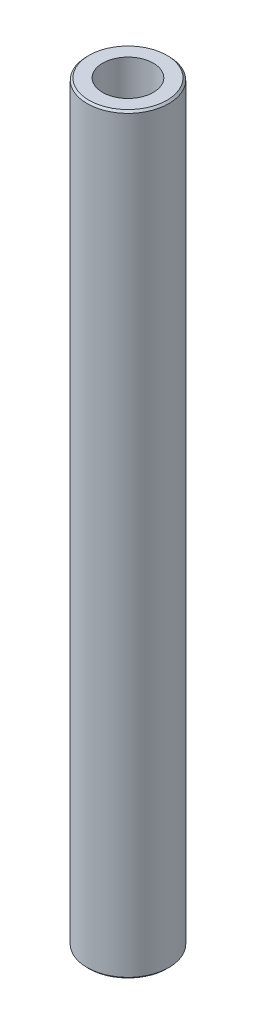
SolidWorks part; units mm, degrees
ref_plane "Front Plane" through (0, 0, 0) normal (0, 0, 1) x (1, 0, 0)
ref_plane "Top Plane" through (0, 0, 0) normal (0, 1, 0) x (1, 0, 0)
ref_plane "Right Plane" through (0, 0, 0) normal (1, 0, 0) x (0, 0, -1)
sketch "Sketch1" plane through (0, 0, 0) normal (0, 1, 0) x (1, 0, 0)
  circle A0 centre (0, 0) radius 12.5
  dimension "SHAFT_OD" = 25
extrude "Boss-Extrude1" add sketch "Sketch1" along normal blind 230.0349
sketch "Sketch2" plane through (0, 0, 0) normal (0, 1, 0) x (1, 0, 0)
  circle A0 centre (0, 0) radius 7.7593
  dimension "BORE_D" = 15.5187
extrude "Cut-Extrude1" cut sketch "Sketch2" along normal through all
chamfer "Chamfer1" distance 0.5904 angle 45 2 edges at (0, 230.0349, 12.5) (0, 0, 12.5)
